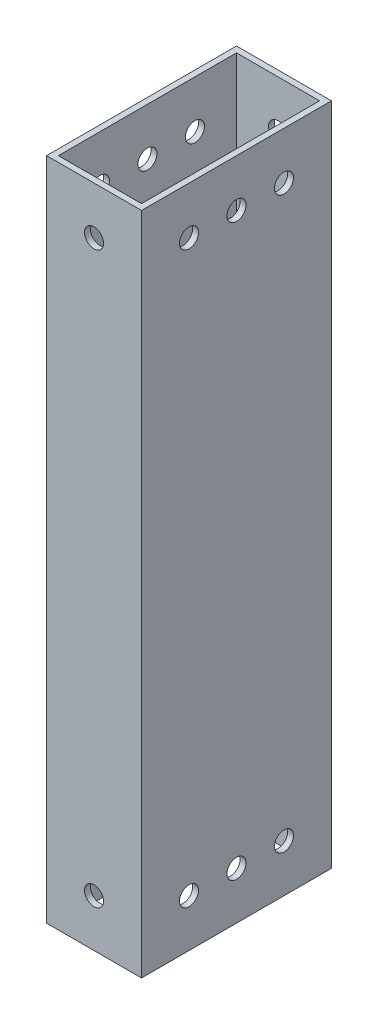
SolidWorks part; units mm, degrees
material "6061-T6 (SS)"
ref_plane "Front" through (0, 0, 0) normal (0, 0, 1) x (1, 0, 0)
ref_plane "Top" through (0, 0, 0) normal (0, 1, 0) x (1, 0, 0)
ref_plane "Right" through (0, 0, 0) normal (1, 0, 0) x (0, 0, -1)
sketch "Sketch1" plane through (0, 0, 0) normal (0, 1, 0) x (1, 0, 0)
  line L1 (12.7, 25.4) -> (-12.7, 25.4)
  line L2 (12.7, 25.4) -> (12.7, -25.4)
  line L3 (12.7, -25.4) -> (-12.7, -25.4)
  line L4 (-12.7, 25.4) -> (-12.7, -25.4)
  line L5 (12.7, 25.4) -> (-12.7, -25.4) construction
  line L6 (12.7, -25.4) -> (-12.7, 25.4) construction
  point P0 (0, 0)
  dimension "D1" = 25.4
  dimension "D2" = 50.8
extrude "Extrude-Thin1" add sketch "Sketch1" along normal up to surface (177.8 mm away) thin thin type one direction reverse wall 1.5875
sketch "Sketch4" plane through (-12.7, 0, 0) normal (-1, 0, 0) x (0, 0, 1)
  line L0 (-12.7, 12.7) -> (12.7, 12.7) construction
  line L3 (-12.7, 165.1) -> (12.7, 165.1) construction
  line L4 (-25.4, 0) -> (25.4, 0) construction
  line L5 (-25.4, 177.8) -> (25.4, 177.8) construction
  point P1 (-12.7, 12.7)
  point P2 (12.7, 12.7)
  point P6 (-12.7, 165.1)
  point P7 (12.7, 165.1)
  point P11 (0, 165.1)
  point P17 (0, 12.7)
  point P27 (-12.7, 165.1)
  point P29 (12.7, 165.1)
  point P31 (-12.7, 12.7)
  point P33 (12.7, 12.7)
  dimension "D1" = 12.7
  dimension "D2" = 12.7
  dimension "D3" = 12.7
hole_wizard "#10 Clearance Hole1" positions "Sketch4" profile "Sketch3" hole size "#10" standard "ANSI Inch" end condition through all
sketch "Sketch3" plane through (-12.7, 12.7, 12.7) normal (0, 1, 0) x (0, 0, 1)
  line L0 (0, 0) -> (0, 25.4)
  line L1 (0, 25.4) -> (2.5527, 25.4)
  line L2 (2.5527, 25.4) -> (2.5527, 0)
  line L5 (2.5527, 0) -> (0, 0)
  line L11 (0, -6.35) -> (0, 107.95) construction
  dimension "Thru Hole Dia." = 5.1054
  dimension "Thru Hole Depth" = 25.4
sketch "Sketch7" plane through (0, 0, 25.4) normal (0, 0, 1) x (1, 0, 0)
  line L0 (-12.7, 0) -> (12.7, 0) construction
  line L1 (-12.7, 177.8) -> (12.7, 177.8) construction
  point P0 (0, 165.1)
  point P2 (0, 12.7)
  dimension "D1" = 12.7
  dimension "D2" = 12.7
hole_wizard "#10 Clearance Hole2" positions "Sketch7" profile "Sketch6" hole size "#10" standard "ANSI Inch" end condition through all
sketch "Sketch6" plane through (0, 165.1, 25.4) normal (1, 0, 0) x (0, -1, 0)
  line L0 (0, 0) -> (0, 50.8)
  line L1 (0, 50.8) -> (2.5527, 50.8)
  line L2 (2.5527, 50.8) -> (2.5527, 0)
  line L5 (2.5527, 0) -> (0, 0)
  line L11 (0, -6.35) -> (0, 107.95) construction
  dimension "Thru Hole Dia." = 5.1054
  dimension "Thru Hole Depth" = 50.8
